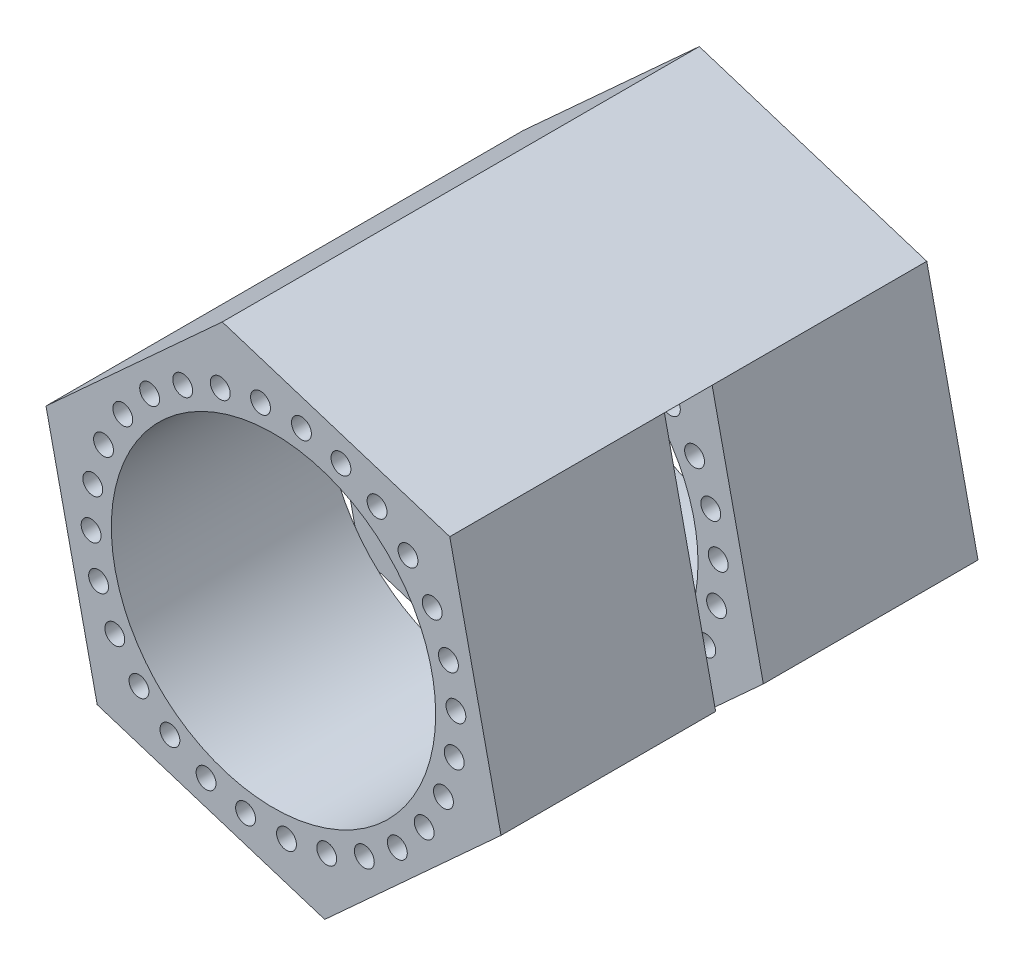
SolidWorks part; units mm, degrees
ref_plane "Front Plane" through (0, 0, 0) normal (1, 0, 0) x (0, 1, 0)
ref_plane "Top Plane" through (0, 0, 0) normal (0, 0, 1) x (0, 1, 0)
ref_plane "Right Plane" through (0, 0, 0) normal (0, 1, 0) x (-1, 0, 0)
sketch "Sketch1" plane through (0, 0, 0) normal (0, 0, 1) x (0, 1, 0)
  line L1 (12.8529, -14.0799) -> (18.62, 4.091)
  line L2 (18.62, 4.091) -> (5.7671, 18.1709)
  line L3 (5.7671, 18.1709) -> (-12.8529, 14.0799)
  line L4 (-12.8529, 14.0799) -> (-18.62, -4.091)
  line L5 (-18.62, -4.091) -> (-5.7671, -18.1709)
  line L6 (-5.7671, -18.1709) -> (12.8529, -14.0799)
  circle A0 centre (0, 0) radius 12.954
  circle A1 centre (0, 0) radius 16.51 construction
  dimension "D1" = 25.908
  dimension "D2" = 33.02
extrude "Boss-Extrude2" add sketch "Sketch1" along normal blind 38.1
sketch "Sketch2" plane through (0, 0, 38.1) normal (0, 0, 1) x (1, 0, 0)
  circle A0 centre (0, 0) radius 14.605 construction
  circle A1 centre (-13.5751, 5.3872) radius 0.7937
  circle A2 centre (-12.036, 8.2729) radius 0.7938
  circle A3 centre (-9.8934, 10.7437) radius 0.7938
  circle A4 centre (-7.2546, 12.6758) radius 0.7938
  circle A5 centre (-4.2521, 13.9723) radius 0.7938
  circle A6 centre (-1.0363, 14.5682) radius 0.7938
  circle A7 centre (2.2314, 14.4335) radius 0.7938
  circle A8 centre (5.3872, 13.5751) radius 0.7937
  circle A9 centre (8.2729, 12.036) radius 0.7937
  circle A10 centre (10.7437, 9.8934) radius 0.7937
  circle A11 centre (12.6758, 7.2546) radius 0.7937
  circle A12 centre (13.9723, 4.2521) radius 0.7938
  circle A13 centre (14.5682, 1.0363) radius 0.7938
  circle A14 centre (14.4335, -2.2314) radius 0.7938
  circle A15 centre (13.5751, -5.3872) radius 0.7937
  circle A16 centre (12.036, -8.2729) radius 0.7938
  circle A17 centre (9.8934, -10.7437) radius 0.7937
  circle A18 centre (7.2546, -12.6758) radius 0.7937
  circle A19 centre (4.2521, -13.9723) radius 0.7937
  circle A20 centre (1.0363, -14.5682) radius 0.7937
  circle A21 centre (-2.2314, -14.4335) radius 0.7937
  circle A22 centre (-5.3872, -13.5751) radius 0.7937
  circle A23 centre (-8.2729, -12.036) radius 0.7937
  circle A24 centre (-10.7437, -9.8934) radius 0.7937
  circle A25 centre (-12.6758, -7.2546) radius 0.7937
  circle A26 centre (-13.9723, -4.2521) radius 0.7938
  circle A27 centre (-14.5682, -1.0363) radius 0.7937
  circle A28 centre (-14.4335, 2.2314) radius 0.7937
  point P62 (0, 0)
  dimension "D1" = 1.5875
  dimension "D2" = 29.21
  dimension "D3" = 28
extrude "Cut-Extrude1" cut sketch "Sketch2" against normal up to surface (38.1 mm away) up to face at (0, 0, 0)
ref_plane "Plane1" through (0, 0, 19.05) normal (0, 0, 1) x (0, -1, 0)
sketch "Sketch3" plane through (0, 0, 19.05) normal (0, 0, 1) x (0, -1, 0)
  line L0 (-12.8529, 14.0799) -> (-8.7335, 9.5672)
  line L1 (-5.7671, -18.1709) -> (-3.9187, -12.3471)
  line L6 (5.7671, 18.1709) -> (-12.8529, 14.0799)
  line L7 (-12.8529, 14.0799) -> (-18.62, -4.091)
  line L8 (-18.62, -4.091) -> (-5.7671, -18.1709)
  line L9 (-5.7671, -18.1709) -> (12.8529, -14.0799)
  line L10 (12.8529, -14.0799) -> (18.62, 4.091)
  line L11 (18.62, 4.091) -> (5.7671, 18.1709)
  line L12 (5.7671, 18.1709) -> (-12.8529, 14.0799)
  line L15 (-5.7671, -18.1709) -> (12.8529, -14.0799)
  line L16 (12.8529, -14.0799) -> (18.62, 4.091)
  line L17 (18.62, 4.091) -> (5.7671, 18.1709)
  circle A0 centre (0, 0) radius 12.954 construction
  arc A1 (-3.9187, -12.3471) -> (-8.7335, 9.5672) centre (0, 0) ccw
  dimension "D1" = 0
extrude "Cut-Extrude3" cut sketch "Sketch3" against normal mid plane 3.81 contours L12 L0 A1 L1 L15 L16 L17
